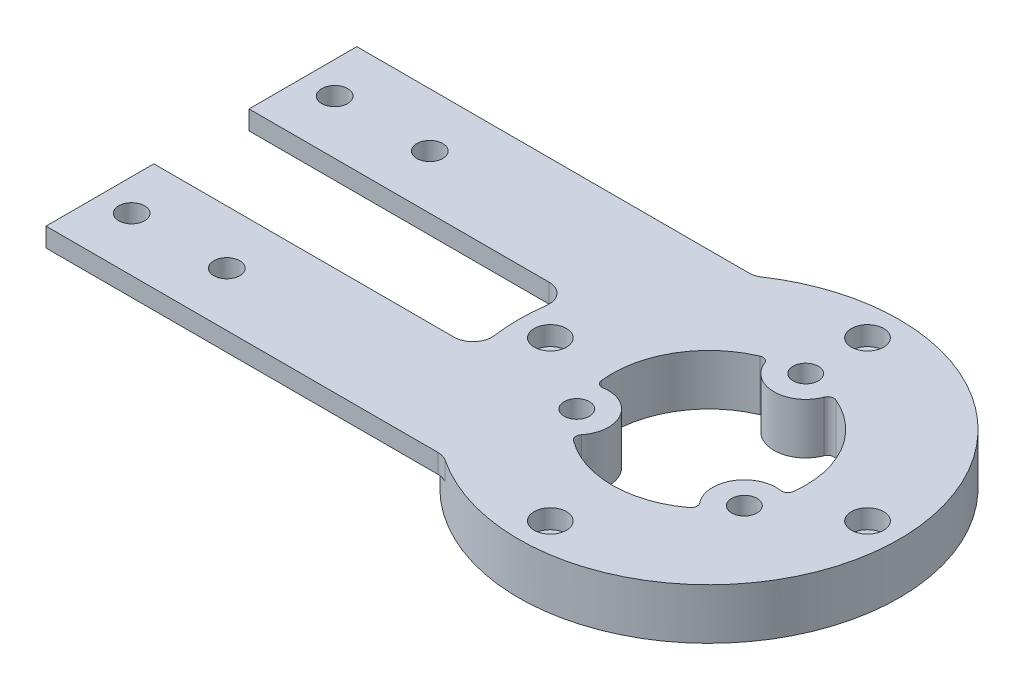
SolidWorks part; units mm, degrees
ref_plane "Front Plane" through (0, 0, 0) normal (0, 0, 1) x (1, 0, 0)
ref_plane "Top Plane" through (0, 0, 0) normal (0, 1, 0) x (1, 0, 0)
ref_plane "Right Plane" through (0, 0, 0) normal (1, 0, 0) x (0, 0, -1)
sketch "Sketch1" plane through (0, 0, 0) normal (0, 1, 0) x (1, 0, 0)
  circle A0 centre (0, 0) radius 30
  circle A1 centre (0, 0) radius 10
  circle A2 centre (0, 0) radius 15.25 construction
  circle A3 centre (0, 15.25) radius 2
  circle A4 centre (13.2069, -7.625) radius 2
  circle A5 centre (-13.2069, -7.625) radius 2
  circle A6 centre (0, 0) radius 25 construction
  circle A7 centre (0, 25) radius 2.55
  circle A8 centre (25, 0) radius 2.55
  circle A9 centre (0, -25) radius 2.55
  circle A10 centre (-25, 0) radius 2.55
  point P13 (0, 0)
  point P15 (0, -31.7807)
  point P16 (0, 0)
  point P24 (0, 0)
  dimension "D1" = 30.5
  dimension "D2" = 60
  dimension "D3" = 20
  dimension "D4" = 4
  dimension "D6" = 5.1
  dimension "D7" = 50
  dimension "D5" = 3
  dimension "D8" = 4
extrude "Boss-Extrude1" add sketch "Sketch1" along normal blind 3
sketch "Sketch2" plane through (0, 3, 0) normal (0, 1, 0) x (1, 0, 0)
  line L1 (-80, 24.5) -> (-17, 24.5)
  line L2 (-80, 24.5) -> (-80, 7.5)
  line L3 (-80, 7.5) -> (-17, 7.5)
  line L4 (-17, 24.5) -> (-17, 7.5)
  line L5 (-80, -7.5) -> (-17, -7.5)
  line L6 (-80, -7.5) -> (-80, -24.5)
  line L7 (-80, -24.5) -> (-17, -24.5)
  line L8 (-17, -7.5) -> (-17, -24.5)
  circle A0 centre (0, 0) radius 10 construction
  dimension "D1" = 17
  dimension "D2" = 15
  dimension "D3" = 7.5
  dimension "D4" = 17
  dimension "D5" = 80
extrude "Boss-Extrude2" add sketch "Sketch2" against normal up to surface (3 mm away) up to face at (0, 0, 30)
sketch "Sketch3" plane through (0, 0, 0) normal (0, -1, 0) x (1, 0, 0)
  circle A0 centre (0, 0) radius 30
  arc A1 (-17.3133, -24.5) -> (-17.3133, 24.5) centre (0, 0) ccw construction
  circle A2 centre (0, -15.25) radius 2 construction
  circle A3 centre (13.2069, 7.625) radius 2 construction
  circle A4 centre (-13.2069, 7.625) radius 2 construction
  circle A5 centre (0, 0) radius 10 construction
  circle A6 centre (0, -15.25) radius 2
  circle A7 centre (13.2069, 7.625) radius 2
  circle A8 centre (-13.2069, 7.625) radius 2
  circle A9 centre (0, 0) radius 10
extrude "Boss-Extrude3" add sketch "Sketch3" along normal blind 5
sketch "Sketch4" plane through (0, 0, 0) normal (0, -1, 0) x (1, 0, 0)
  line L0 (-80, 24.5) -> (-80, 7.5) construction
  line L1 (-80, 7.5) -> (-29.0474, 7.5) construction
  line L2 (-80, -24.5) -> (-17.3133, -24.5) construction
  circle A0 centre (-75, 16) radius 2.05
  circle A1 centre (-60, 16) radius 2.05
  circle A2 centre (-75, -16) radius 2.05
  circle A3 centre (-60, -16) radius 2.05
  dimension "D1" = 4.1
  dimension "D2" = 5
  dimension "D3" = 15
  dimension "D4" = 8.5
  dimension "D5" = 8.5
extrude "Cut-Extrude1" cut sketch "Sketch4" against normal through all
fillet "Fillet1" radius 3 4 edges at (-17.3133, 1.5, -24.5) (-29.0474, 1.5, -7.5) (-29.0474, 1.5, 7.5) (-17.3133, 1.5, 24.5)
sketch "Sketch5" plane through (0, 3, 0) normal (0, 1, 0) x (1, 0, 0)
  arc A0 (-4.9324, 14.4303) -> (4.9324, 14.4303) centre (0, 15.25) ccw
  arc A1 (14.9632, -2.9436) -> (10.0309, -11.4867) centre (13.2069, -7.625) ccw
  arc A2 (-10.0309, -11.4867) -> (-14.9632, -2.9436) centre (-13.2069, -7.625) ccw
  arc A3 (-4.9324, 14.4303) -> (-14.9632, -2.9436) centre (0, 0) ccw
  circle A4 centre (0, 15.25) radius 2 construction
  arc A5 (-10.0309, -11.4867) -> (10.0309, -11.4867) centre (0, 0) ccw
  arc A6 (14.9632, -2.9436) -> (4.9324, 14.4303) centre (0, 0) ccw
  dimension "D1" = 3
extrude "Cut-Extrude2" cut sketch "Sketch5" against normal through all
fillet "Fillet2" radius 1 6 edges at (10.0309, -1, 11.4867) (-10.0309, -1, 11.4867) (-14.9632, -1, 2.9436) (14.9632, -1, 2.9436) (4.9324, -1, -14.4303) (-4.9324, -1, -14.4303)
